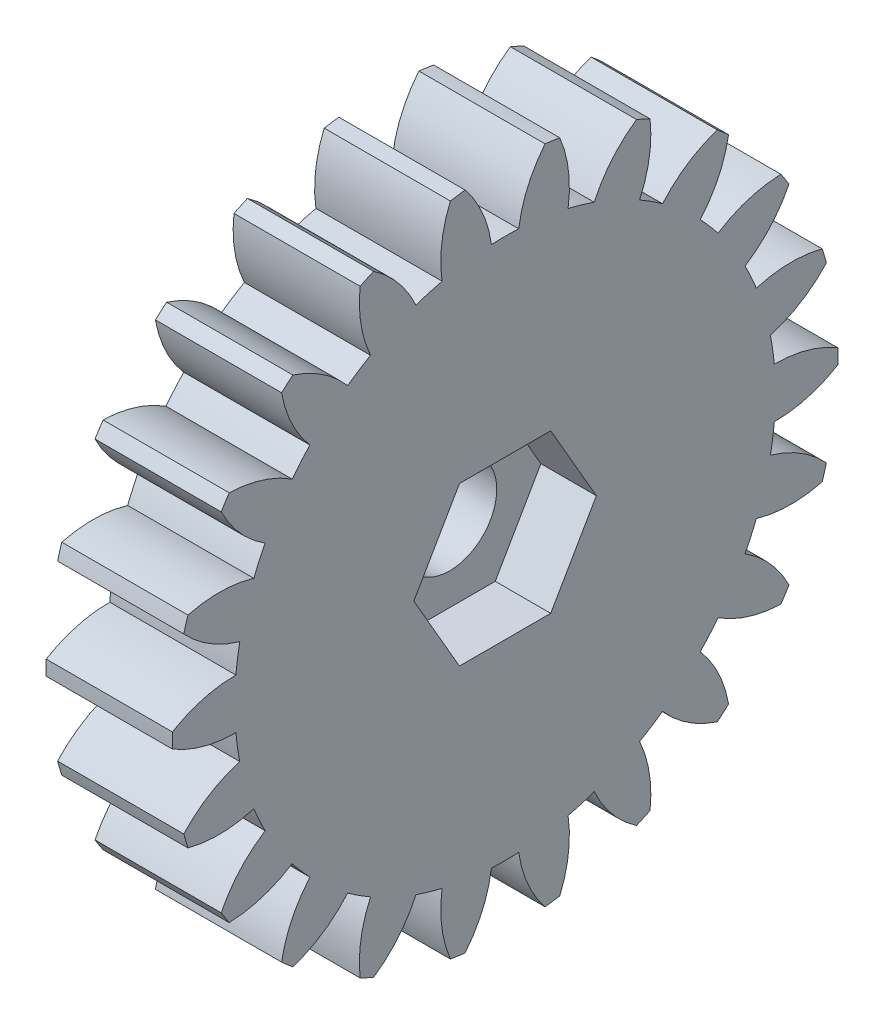
SolidWorks part; units mm, degrees
ref_plane "Plane1" through (0, 0, 0) normal (0, 0, 1) x (1, 0, 0)
ref_plane "Plane2" through (0, 0, 0) normal (0, 1, 0) x (1, 0, 0)
ref_plane "Plane3" through (0, 0, 0) normal (1, 0, 0) x (0, 0, -1)
sketch "HoldingSke" plane through (0, 0, 0) normal (0, 1, 0) x (1, 0, 0)
  line L0 (0, 0) -> (0.9272, -0.3746)
  line L1 (-15, 0) -> (100, 0) construction
  line L2 (0, 0) -> (-2.1039, 2.3779)
  line L3 (0, 0) -> (-11.863, 4.5341)
  line L4 (0, 0) -> (8.0072, 3.2351)
  line L5 (0, 0) -> (-46.8476, -17.4728)
  line L6 (0, 0) -> (-3.7718, -2.5448)
  line L7 (-2.1039, 2.3779) -> (8.6586, 51.2059)
  line L8 (-76.2, 54.61) -> (-75.5, 54.61)
  line L9 (-71.009, 38.7566) -> (-53.1078, 45.2721)
  line L10 (-76.2, 71.12) -> (104.1128, 71.12)
  line L11 (0, 0) -> (-4.55, 0)
  line L12 (-76.2, 101.6) -> (-76.162, 101.6)
  line L13 (24.9733, 27.94) -> (52.9518, 28.4284)
  line L14 (24.9733, 27.94) -> (24.9743, 27.94)
  line L15 (24.9733, 27.94) -> (100.4006, 29.5858)
  line L16 (-63.627, -1) -> (-12.827, -1)
  circle A0 centre (0, 0) radius 2
  circle A1 centre (0, 0) radius 9.749
  circle A2 centre (0, 0) radius 37.5
  circle A3 centre (0, 0) radius 2
  dimension "Num_teeth" = 22
  dimension "Pitch_radius" = 180.3128
  dimension "Width" = 4.55
  dimension "Thickness" = 4.55
sketch "BasProSke" plane through (0, 0, 0) normal (0, 1, 0) x (1, 0, 0)
  line L0 (-10, 0) -> (60, 0) construction
  line L1 (0, 0) -> (0, 12)
  line L2 (0, 0) -> (4.55, 0)
  line L3 (4.55, 0) -> (4.55, 12)
  line L4 (4.55, 12) -> (0, 12)
  dimension "Thickness" = 4.55
  dimension "Diameter" = 24
revolve "Base-Revolve" add sketch "BasProSke" angle 360 about L0
sketch "TooCutSke" plane through (0, 0, 0) normal (1, 0, 0) x (0, 0, -1)
  line L1 (0, 0) -> (0, 107) construction
  line L2 (0, 0) -> (-0.8512, 10.967) construction
  line L3 (0, 0) -> (-3.1242, 21.7296) construction
  line L4 (-0.8512, 10.967) -> (-1.5621, 10.8648) construction
  arc A0 (0.491, 9.7366) -> (-0.491, 9.7366) centre (0, 0) ccw
  arc A1 (1.4609, 11.9363) -> (-1.4609, 11.9363) centre (0, 0) ccw
  circle A2 centre (0, 0) radius 11 construction
  circle A3 centre (0, 0) radius 10.3366 construction
  arc A4 (-0.491, 9.7366) -> (-1.4609, 11.9363) centre (-4.8488, 9.1288) ccw
  arc A5 (1.4609, 11.9363) -> (0.491, 9.7366) centre (4.8488, 9.1288) ccw
extrude "ToothCut" cut sketch "TooCutSke" along normal through all
fillet "Breaks" [suppressed] radius 0.02 tangent propagation no
fillet "RootFillets" [suppressed] radius 0.251
pattern_circular "TeethCuts" count 22 every 16.364 about axis through (-10, 0, 0) along (1, 0, 0) of "ToothCut", "RootFillets", "Breaks"
sketch "HubNeaOneSke" plane through (0, 0, 0) normal (-1, 0, 0) x (0, 0, 1)
  circle A0 centre (0, 0) radius 9.749
  dimension "Diameter" = 19.498
extrude "HubNearOne" [suppressed] add sketch "HubNeaOneSke" along normal blind 45.4501
sketch "HubNeaBotSke" plane through (0, 0, 0) normal (-1, 0, 0) x (0, 0, 1)
  circle A0 centre (0, 0) radius 9.749
  dimension "Diameter" = 19.498
extrude "HubNearBoth" [suppressed] add sketch "HubNeaBotSke" along normal blind 22.725
ref_plane "FarPln" through (4.55, 0, 0) normal (1, 0, 0) x (0, 0, -1)
sketch "HubFarSke" plane through (4.55, 0, 0) normal (1, 0, 0) x (0, 0, -1)
  circle A0 centre (0, 0) radius 9.749
  dimension "Diameter" = 19.498
extrude "HubFar" [suppressed] add sketch "HubFarSke" along normal blind 22.725
sketch "BorSke" plane through (0, 0, 0) normal (1, 0, 0) x (0, 0, -1)
  circle A0 centre (0, 0) radius 1.7
  dimension "Diameter" = 3.4
extrude "Bore" cut sketch "BorSke" along normal mid plane 100.0001
sketch "KeySke" plane through (0, 0, 0) normal (1, 0, 0) x (0, 0, -1)
  line L0 (-0.8, 0) -> (-0.8, 2.7)
  line L1 (-0.8, 2.7) -> (0.8, 2.7)
  line L2 (0.8, 2.7) -> (0.8, 0)
  line L3 (0, 0) -> (0, 34) construction
  line L4 (-0.8, 0) -> (0.8, 0)
  dimension "Width" = 1.6
extrude "Keyway" [suppressed] cut sketch "KeySke" along normal mid plane 100.0001
pattern_circular "Keyway2" [suppressed] count 2 every 90 about axis through (-10, 0, 0) along (1, 0, 0) reverse direction yes
sketch "Sketch1" plane through (0, 0, 0) normal (-1, 0, 0) x (0, 0, 1)
  line L1 (-2.5, -2.5) -> (2.5, -2.5)
  line L2 (-2.5, -2.5) -> (-2.5, 2.5)
  line L3 (-2.5, 2.5) -> (2.5, 2.5)
  line L4 (2.5, -2.5) -> (2.5, 2.5)
  line L5 (-2.5, -2.5) -> (2.5, 2.5) construction
  line L6 (-2.5, 2.5) -> (2.5, -2.5) construction
  circle A0 centre (0, 0) radius 5
  circle A1 centre (0, 0) radius 6
  point P0 (0, 0)
  dimension "D3" = 10
  dimension "D4" = 1
  dimension "D1" = 5
  dimension "D2" = 5
extrude "Boss-Extrude1" add sketch "Sketch1" along normal blind 2 contours A0
extrude "Cut-Extrude1" cut sketch "Sketch1<2>" against normal offset from surface (2.55 mm away) 4 from surface contours L1 L4 L3 L2 region at (0, 0, 0) up to face at (4.55, 0, 1.7) starting at face at (-2, 0, 5)
sketch "Sketch1<2>" plane through (0, 0, 0) normal (-1, 0, 0) x (0, 0, 1) same geometry as "Sketch1"
extrude "Boss-Extrude2" add sketch "Sketch1<4>" along normal blind 1 contours A1 A0 region at (0, 0, -5.8303)
sketch "Sketch1<4>" plane through (0, 0, 0) normal (-1, 0, 0) x (0, 0, 1) same geometry as "Sketch1"
sketch "Sketch2" plane through (4.55, 0, 0) normal (1, 0, 0) x (0, 0, -1)
  line L1 (1.6454, 2.85) -> (-1.6454, 2.85)
  line L2 (-1.6454, 2.85) -> (-3.2909, 0)
  line L3 (-3.2909, 0) -> (-1.6454, -2.85)
  line L4 (-1.6454, -2.85) -> (1.6454, -2.85)
  line L5 (1.6454, -2.85) -> (3.2909, 0)
  line L6 (3.2909, 0) -> (1.6454, 2.85)
  circle A0 centre (0, 0) radius 2.85 construction
  dimension "D1" = 5.7
extrude "Cut-Extrude2" cut sketch "Sketch2" against normal blind 2
equation "' \"Module@HoldingSke\" = 6.35"
equation "' \"Num_teeth@HoldingSke\" = 12"
equation "' \"Ap@HoldingSke\" =  20"
equation "' \"Ap@HoldingSke\" = 20"
equation "' \"Width@HoldingSke\" = 0.5 * 25.4"
equation "' \"Hub_dia@HoldingSke\"= 1 * 25.4"
equation "' \"Hub_dia@HoldingSke\" = 1 * 25.4"
equation "' \"Overall_len@HoldingSke\" = 1.0 * 25.4"
equation "' \"Bore@HoldingSke\" = 0.75 * 25.4"
equation "' \"T_dim@HoldingSke\" = 0.1 * 25.4"
equation "' \"Width@KeySke\" = 0.25 * 25.4"
equation "' \"Show_teeth@HoldingSke\" = 13"
equation "' \"Backlash@HoldingSke\" = 0.009 * 25.4"
equation "' \"Addendum_fac@HoldingSke\" = 1.0"
equation "' \"Dedendum_fac@HoldingSke\" = 1.25"
equation "' \"Dedendum_add@HoldingSke\" = 0.00005 * 25.4"
equation "' \"Clearance_fac@HoldingSke\" = 0.25"
equation "\"Pitch@HoldingSke\" = 1 / \"Module@HoldingSke\""
equation "\"Overcut_dia@TooCutSke\" = (\"Num_teeth@HoldingSke\" + 2 * \"Addendum_fac@HoldingSke\") / \"Pitch@HoldingSke\" + 0.002 * 25.4"
equation "\"Pitch_dia@TooCutSke\" = \"Num_teeth@HoldingSke\" / \"Pitch@HoldingSke\""
equation "\"Base_dia@TooCutSke\" = \"Num_teeth@HoldingSke\" / \"Pitch@HoldingSke\" * cos((\"Ap@HoldingSke\"  * 3.14159265 / 180))"
equation "\"Root_dia@TooCutSke\" = (\"Num_teeth@HoldingSke\" + 2) / \"Pitch@HoldingSke\" - 2 * (\"Addendum_fac@HoldingSke\" + \"Dedendum_fac@HoldingSke\") / \"Pitch@HoldingSke\" - \"Dedendum_add@HoldingSke\" * 2"
equation "\"Half_ang@TooCutSke\" = 180 / \"Num_teeth@HoldingSke\""
equation "\"Half_CT@TooCutSke\" = \"Num_teeth@HoldingSke\" / \"Pitch@HoldingSke\" * sin((3.14159265 / 2 / \"Num_teeth@HoldingSke\")) / 2 - 7 * \"Backlash@HoldingSke\" / 4"
equation "\"Flank_rad@TooCutSke\" = \"Num_teeth@HoldingSke\" / \"Pitch@HoldingSke\" / 5"
equation "\"Radius@RootFillets\" = \"Clearance_fac@HoldingSke\" / \"Pitch@HoldingSke\" + \"Dedendum_add@HoldingSke\""
equation "\"Break_rad@Breaks\" = 0.02 / \"Pitch@HoldingSke\""
equation "\"Thickness@HoldingSke\" = \"Width@HoldingSke\""
equation "\"OAL@HoldingSke\" = \"Thickness@HoldingSke\""
equation "\"MHD@HoldingSke\" = (\"Num_teeth@HoldingSke\" + 2) / \"Pitch@HoldingSke\" - 2 * (\"Addendum_fac@HoldingSke\" + \"Dedendum_fac@HoldingSke\")  / \"Pitch@HoldingSke\" - \"Dedendum_add@HoldingSke\" * 2"
equation "\"MBD@HoldingSke\" = (\"Num_teeth@HoldingSke\" + 2) / \"Pitch@HoldingSke\" - 2 * (\"Addendum_fac@HoldingSke\" + \"Dedendum_fac@HoldingSke\")  / \"Pitch@HoldingSke\" - \"Dedendum_add@HoldingSke\" * 2 - 0.002 * 25.4"
equation "\"MHD@HoldingSke\" = ((sgn( \"MHD@HoldingSke\" - \"Hub_dia@HoldingSke\" )-1)*( \"MHD@HoldingSke\" - \"Hub_dia@HoldingSke\" ))/-2+ \"Hub_dia@HoldingSke\""
equation "\"MBD@HoldingSke\" = ((sgn( \"MBD@HoldingSke\" - \"Bore@HoldingSke\" )-1)*( \"MBD@HoldingSke\" - \"Bore@HoldingSke\" ))/-2+ \"Bore@HoldingSke\""
equation "\"OAL@HoldingSke\" = ((sgn( \"OAL@HoldingSke\" - \"Overall_len@HoldingSke\" )+1)*( \"OAL@HoldingSke\" - \"Overall_len@HoldingSke\" ))/2 + \"Overall_len@HoldingSke\" + 0.000002 * 25.4"
equation "\"Num_teeth@TeethCuts\" = int( \"Show_teeth@HoldingSke\" ) + 1"
equation "\"Num_teeth@TeethCuts\" = ((sgn( \"Num_teeth@TeethCuts\" - \"Num_teeth@HoldingSke\" )-1)*( \"Num_teeth@TeethCuts\" - \"Num_teeth@HoldingSke\" ))/-2+ \"Num_teeth@HoldingSke\""
equation "\"Num_teeth@TeethCuts\" = ((sgn( \"Num_teeth@TeethCuts\" - 2.0)+1)*( \"Num_teeth@TeethCuts\" - 2.0))/2 +2.0"
equation "\"Angle@TeethCuts\" = 360.0 / \"Num_teeth@HoldingSke\""
equation "\"Diameter@BasProSke\" = (\"Num_teeth@HoldingSke\" + 2 * \"Addendum_fac@HoldingSke\") / \"Pitch@HoldingSke\""
equation "\"Thickness@BasProSke\"  = \"Thickness@HoldingSke\""
equation "' \"Fillet_rad@BasProSke\" =  \"Thickness@HoldingSke\" * 0.05"
equation "' \"Fillet_rad@BasProSke\" = \"Thickness@HoldingSke\" * 0.05"
equation "\"MHD@HoldingSke\" = ((sgn( \"MHD@HoldingSke\" - \"Root_dia@TooCutSke\" )-1)*( \"MHD@HoldingSke\" - \"Root_dia@TooCutSke\" ))/-2+ \"Root_dia@TooCutSke\""
equation "\"Diameter@HubNeaOneSke\" = \"MHD@HoldingSke\""
equation "\"Length@HubNearOne\" = \"OAL@HoldingSke\" - \"Thickness@BasProSke\""
equation "\"Diameter@HubNeaBotSke\" = \"MHD@HoldingSke\""
equation "\"Length@HubNearBoth\" = ( \"OAL@HoldingSke\" - \"Thickness@BasProSke\" ) / 2.0"
equation "\"Thickness@FarPln\" = \"Thickness@BasProSke\""
equation "\"Diameter@HubFarSke\" = \"MHD@HoldingSke\""
equation "\"Length@HubFar\" = ( \"OAL@HoldingSke\" - \"Thickness@BasProSke\" ) / 2.0"
equation "\"Diameter@BorSke\"=3.4"
equation "\"D1@Bore\" = \"OAL@HoldingSke\" * 2.0"
equation "\"D1@Keyway\" = \"OAL@HoldingSke\" * 2.0"
equation "\"Offset@KeySke\" = \"T_dim@HoldingSke\" + \"MBD@HoldingSke\" / 2.0"
